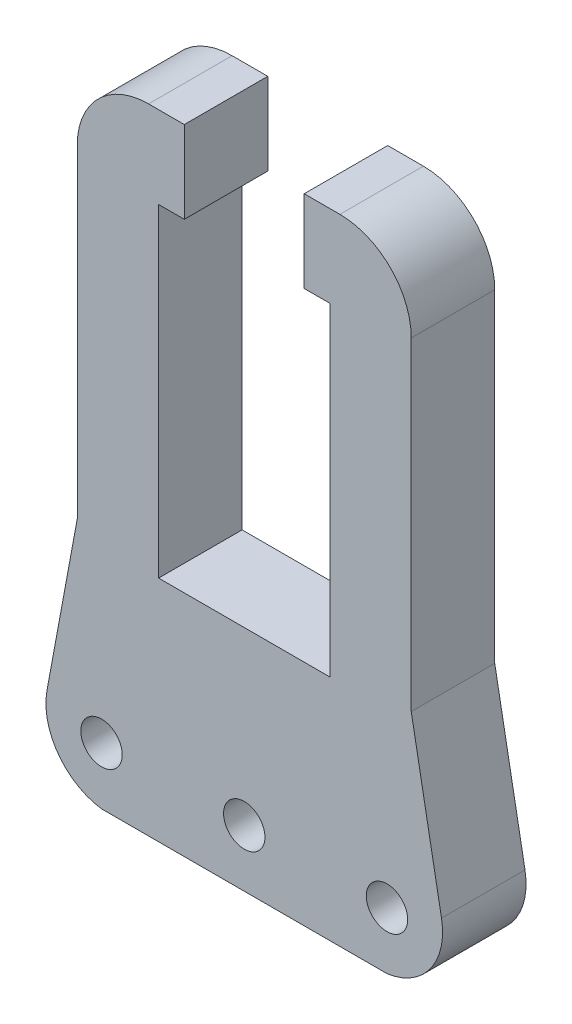
SolidWorks part; units mm, degrees
material "Acrylic (Medium-high impact)"
ref_plane "Front Plane" through (0, 0, 0) normal (0, 0, 1) x (1, 0, 0)
ref_plane "Top Plane" through (0, 0, 0) normal (0, 1, 0) x (1, 0, 0)
ref_plane "Right Plane" through (0, 0, 0) normal (1, 0, 0) x (0, 0, -1)
sketch "Model" plane through (0, 0, 0) normal (0, 0, 1) x (1, 0, 0)
  line L0 (519.9822, -457.799) -> (519.9822, 49542.201) construction
  line L1 (508.2822, 554.9348) -> (506.1623, 543.4616)
  line L2 (519.9822, 542.1848) -> (509.9822, 542.1848) construction
  line L3 (513.9822, 554.1848) -> (525.9822, 554.1848)
  line L4 (509.9822, 538.1848) -> (529.9822, 538.1848)
  line L5 (508.2822, 577.6043) -> (508.2822, 554.9348)
  line L6 (515.7822, 582.6043) -> (513.2822, 582.6043)
  line L7 (515.7822, 576.8543) -> (515.7822, 582.6043)
  line L8 (513.9822, 576.8543) -> (515.7822, 576.8543)
  line L9 (513.9822, 554.1848) -> (513.9822, 576.8543)
  line L10 (519.9822, 542.1848) -> (529.9822, 542.1848) construction
  line L80 (525.9822, 554.1848) -> (525.9822, 576.8543)
  line L81 (525.9822, 576.8543) -> (524.1822, 576.8543)
  line L82 (524.1822, 576.8543) -> (524.1822, 582.6043)
  line L83 (524.1822, 582.6043) -> (526.6822, 582.6043)
  line L84 (531.6822, 577.6043) -> (531.6822, 554.9348)
  line L85 (531.6822, 554.9348) -> (533.8022, 543.4616)
  circle A0 centre (509.9822, 542.1848) radius 1.45
  arc A1 (526.6822, 582.6043) -> (531.6822, 577.6043) centre (526.6822, 577.6043) cw
  arc A2 (506.1623, 543.4616) -> (509.9822, 538.1848) centre (510.5874, 542.644) ccw
  arc A3 (533.8022, 543.4616) -> (529.9822, 538.1848) centre (529.3771, 542.644) cw
  arc A4 (513.2822, 582.6043) -> (508.2822, 577.6043) centre (513.2822, 577.6043) ccw
  circle A5 centre (519.9822, 542.1848) radius 1.45
  circle A6 centre (529.9822, 542.1848) radius 1.45
  point P2 (519.9822, 554.1848)
  point P5 (519.9822, 538.1848)
  point P6 (519.9822, 554.1848)
  point P13 (519.9822, 538.1848)
  dimension "D4" = 2.9
  dimension "D9" = 4.5
  dimension "D11" = 5
  dimension "D1" = 12
  dimension "D2" = 22.6695
  dimension "D3" = 10
  dimension "D5" = 4
  dimension "D6" = 12
  dimension "D7" = 5.75
  dimension "D8" = 1.8
  dimension "D10" = 11.4732
  dimension "D12" = 20
  dimension "D13" = 2.5
extrude "Boss-Extrude1" add sketch "Model" along normal blind 5.85
